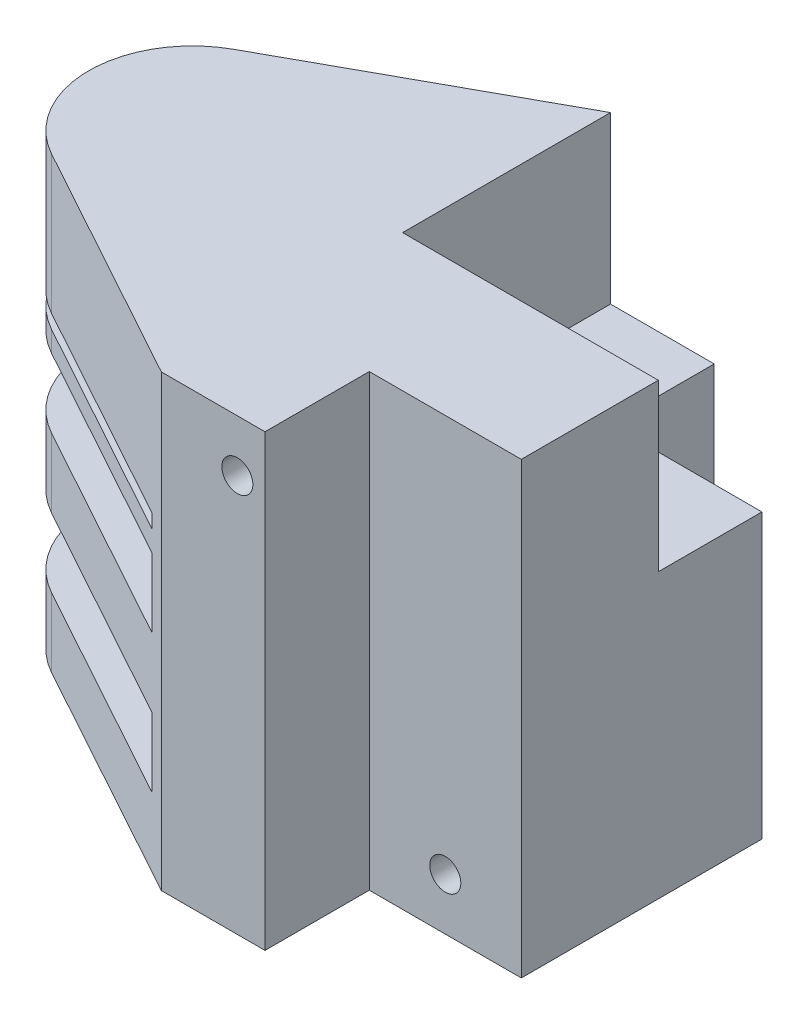
SolidWorks part; units mm, degrees
material "Copper"
ref_plane "Front Plane" through (0, 0, 0) normal (0, 0, 1) x (1, 0, 0)
ref_plane "Top Plane" through (0, 0, 0) normal (0, 1, 0) x (1, 0, 0)
ref_plane "Right Plane" through (0, 0, 0) normal (1, 0, 0) x (0, 0, -1)
sketch "Sketch1" plane through (0, 0, 0) normal (0, 0, 1) x (1, 0, 0)
  line L1 (0, 0) -> (80, 0)
  line L2 (0, 0) -> (0, 65)
  line L3 (0, 65) -> (80, 65)
  line L4 (80, 0) -> (80, 65)
  dimension "D1" = 65
  dimension "D2" = 80
extrude "Boss-Extrude1" add sketch "Sketch1" along normal blind 65
sketch "Sketch3" plane through (0, 0, 0) normal (0, -1, 0) x (1, 0, 0)
  line L0 (80, 32.5) -> (0, 32.5) construction
  line L1 (80, 65) -> (80, 0) construction
  line L2 (0, 65) -> (0, 0) construction
  line L3 (58, 49.91) -> (58, 32.5) construction
  line L4 (80, 65) -> (58, 65)
  line L5 (80, 65) -> (80, 49.91)
  line L6 (80, 49.91) -> (58, 49.91)
  line L7 (58, 65) -> (58, 49.91)
  line L8 (80, 0) -> (58, 0)
  line L9 (80, 0) -> (80, 15.09)
  line L10 (80, 15.09) -> (58, 15.09)
  line L11 (58, 0) -> (58, 15.09)
  line L12 (58, 32.5) -> (58, 15.09) construction
  dimension "D1" = 22
  dimension "D2" = 17.41
extrude "Cut-Extrude1" cut sketch "Sketch3" against normal blind 65.72
sketch "Sketch4" plane through (0, 0, 49.91) normal (0, 0, 1) x (1, 0, 0)
  line L0 (69, 0) -> (69, 65) construction
  line L1 (58, 0) -> (80, 0) construction
  line L2 (69, 7.5) -> (69, 0) construction
  line L3 (58, 65) -> (80, 65) construction
  line L4 (69, 65) -> (69, 57.5) construction
  line L5 (69, 57.5) -> (54, 57.5) construction
  circle A0 centre (69, 7.5) radius 2.2451
  circle A1 centre (69, 57.5) radius 2.2451
  circle A2 centre (54, 57.5) radius 2.245
  dimension "D1" = 4.4901
  dimension "D3" = 7.5
  dimension "D4" = 4.4901
  dimension "D5" = 4.49
  dimension "D2" = 7.5
  dimension "D6" = 15
extrude "Cut-Extrude2" cut sketch "Sketch4" against normal blind 55.72 and the other way blind 20 contours A2 | A0 region at (54, 57.5, 49.91)
sketch "Sketch5" plane through (0, 0, 0) normal (-1, 0, 0) x (0, 0, 1)
  line L0 (65, 65) -> (65, 0) construction
  line L1 (0, 0) -> (65, 0)
  line L2 (0, 0) -> (0, 10)
  line L3 (0, 10) -> (65, 10)
  line L4 (65, 0) -> (65, 10)
  line L6 (0, 10) -> (65, 10)
  line L7 (0, 10) -> (0, 20)
  line L8 (0, 20) -> (65, 20)
  line L9 (65, 10) -> (65, 20)
  line L10 (0, 20) -> (65, 20)
  line L11 (0, 20) -> (0, 30)
  line L12 (0, 30) -> (65, 30)
  line L13 (65, 20) -> (65, 30)
  line L14 (0, 30) -> (65, 30)
  line L15 (0, 30) -> (0, 40)
  line L16 (0, 40) -> (65, 40)
  line L17 (65, 30) -> (65, 40)
  line L18 (0, 40) -> (65, 40)
  line L19 (0, 40) -> (0, 43)
  line L20 (0, 43) -> (65, 43)
  line L21 (65, 40) -> (65, 43)
  line L22 (0, 43) -> (65, 43)
  line L23 (0, 43) -> (0, 45)
  line L24 (0, 45) -> (65, 45)
  line L25 (65, 43) -> (65, 45)
  line M3 (0, 65) -> (0, 0)
  line M5 (65, 0) -> (65, 65)
  dimension "D1" = 10
  dimension "D2" = 3
  dimension "D3" = 2
extrude "Cut-Extrude3" cut sketch "Sketch5" against normal blind 40 contours L16 L12 M3 M5 | L8 L3 M3 M5 | L23 L24 L25 L22 region at (0, 15, 32.5) region at (0, 35, 32.5)
sketch "Sketch23" plane through (0, 65, 0) normal (0, 1, 0) x (1, 0, 0)
  line L0 (80, -49.91) -> (80, -15.09) construction
  line L1 (43, 0) -> (80, 0)
  line L2 (43, 0) -> (43, -30.09)
  line L3 (43, -30.09) -> (80, -30.09)
  line L4 (80, 0) -> (80, -30.09)
  line L5 (58, 0) -> (0, 0) construction
  line L6 (80, -15.09) -> (58, -15.09) construction
  dimension "D1" = 37
  dimension "D2" = 15
extrude "Cut-Extrude15" cut sketch "Sketch23" against normal blind 24
sketch "Sketch6" plane through (0, 0, 0) normal (0, -1, 0) x (1, 0, 0)
  line L0 (0, 32.5) -> (48.8784, 32.5) construction
  line L1 (0, 65) -> (0, 0) construction
  line L2 (58, 0) -> (43, 0)
  line L3 (0, 0) -> (58, 0) construction
  line L4 (43, 0) -> (7.7767, 19.3538)
  line L5 (7.7767, 45.6462) -> (43, 65)
  line L6 (0, 65) -> (58, 65) construction
  line L7 (43, 0) -> (43, 65) construction
  line L8 (58, 15.09) -> (58, 0) construction
  line L9 (43, 14.0738) -> (58, 14.0738) construction
  line L10 (43, 0) -> (0, 0)
  line L11 (0, 0) -> (0, 32.5)
  line L12 (0, 32.5) -> (0, 65)
  line L13 (0, 65) -> (43, 65)
  circle A0 centre (15, 32.5) radius 15
  line M6 (58, 65) -> (0, 65)
  line M7 (0, 65) -> (0, 0)
  line M8 (0, 0) -> (58, 0)
  dimension "D1" = 15
  dimension "D2" = 30
extrude "Cut-Extrude4" cut sketch "Sketch6" against normal blind 65 contours A0 L4 M7 M8 | A0 L5 M6 M7 region at (14.0187, 0, 8.2899) region at (14.0187, 0, 56.7101)
sketch "Sketch10" plane through (0, 0, 0) normal (0, -1, 0) x (1, 0, 0)
  line L0 (0, 32.5) -> (15, 32.5) construction
  arc A0 (7.7767, 45.6462) -> (7.7767, 19.3538) centre (15, 32.5) ccw construction
  circle A1 centre (15, 32.5) radius 1
  dimension "D1" = 15
  dimension "D2" = 2
extrude "Cut-Extrude6" cut sketch "Sketch10" against normal blind 42
